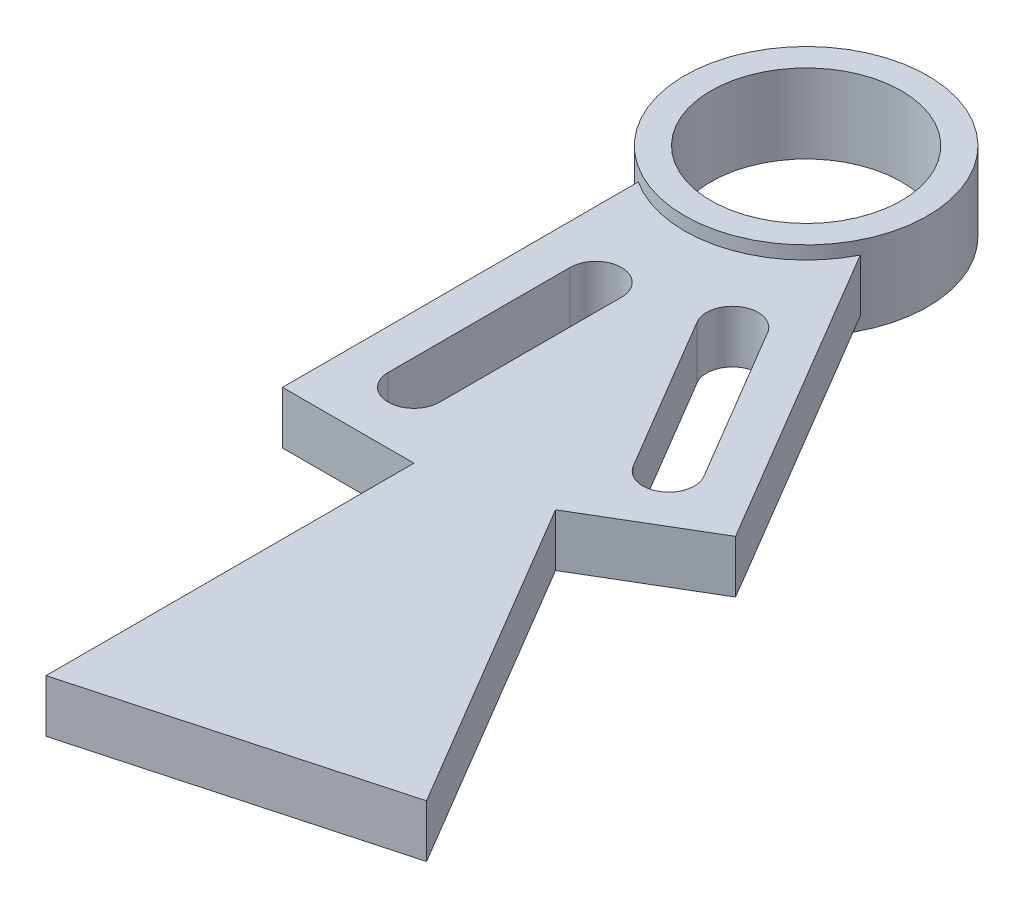
SolidWorks part; units mm, degrees
material "AISI 4130 Steel, annealed at 865C"
ref_plane "Front Plane" through (0, 0, 0) normal (0, 0, 1) x (1, 0, 0)
ref_plane "Top Plane" through (0, 0, 0) normal (0, 1, 0) x (1, 0, 0)
ref_plane "Right Plane" through (0, 0, 0) normal (1, 0, 0) x (0, 0, -1)
sketch "Sketch1" plane through (0, 0, 0) normal (0, 1, 0) x (1, 0, 0)
  line L0 (0, -50.4952) -> (0, -14.6812) construction
  line L1 (25.7368, -43.444) -> (7.4828, -12.6311) construction
  line L2 (0, -47.3837) -> (0, -25.4127) construction
  line L5 (-3.1115, -47.3837) -> (-3.1115, -25.4127)
  line L8 (-7.9375, -55.3212) -> (7.9375, -55.3212)
  line L9 (21.3674, -51.6418) -> (35.0256, -43.5505)
  line L10 (-7.9375, -55.3212) -> (-7.9375, -12.3505)
  line L11 (35.0256, -43.5505) -> (13.124, -6.5802)
  line L12 (7.9375, -55.3212) -> (7.9375, -99.7712)
  line L13 (21.3674, -51.6418) -> (44.023, -89.8848)
  line L14 (7.9375, -99.7712) -> (44.023, -89.8848)
  line L15 (0, -14.6812) -> (0, 0) construction
  line L16 (0, -55.3212) -> (0, -50.4952) construction
  line L17 (28.1965, -47.5961) -> (25.7368, -43.444)
  line L18 (3.1115, -47.3837) -> (3.1115, -25.4127)
  line L19 (12.9525, -21.8641) -> (24.1509, -40.767) construction
  line L20 (15.6295, -20.2782) -> (26.8279, -39.1811)
  line L21 (10.2755, -23.45) -> (21.4739, -42.3529)
  line L22 (7.4828, -12.6311) -> (0, 0) construction
  line L23 (0, 0) -> (20.1347, -73.4917) construction
  line L25 (181.4136, -306.2286) -> (14.7666, -24.9262) construction
  line L27 (0, 0) -> (25.9803, -94.828) construction
  circle A0 centre (0, 0) radius 11.5062
  circle A1 centre (0, 0) radius 14.6812
  arc A2 (-3.1115, -47.3837) -> (3.1115, -47.3837) centre (0, -47.3837) ccw
  arc A3 (3.1115, -25.4127) -> (-3.1115, -25.4127) centre (0, -25.4127) ccw
  arc A4 (15.6295, -20.2782) -> (10.2755, -23.45) centre (12.9525, -21.8641) ccw
  arc A5 (21.4739, -42.3529) -> (26.8279, -39.1811) centre (24.1509, -40.767) ccw
  point P9 (0, -36.3982)
  point P14 (18.5517, -31.3155)
  point P23 (0, -55.3212)
  point P26 (28.1965, -47.5961)
  point P33 (0, -50.4952)
  point P36 (25.7368, -43.444)
  point P38 (0, -22.3012)
  dimension "D2" = 29.3624
  dimension "D3" = 40.64
  dimension "D4" = 4.826
  dimension "D6" = 44.45
  dimension "D7" = 7.9375
  dimension "D5" = 4.826
  dimension "D8" = 7.62
  dimension "D9" = 76.2
extrude "Bearing extrude" add sketch "Sketch1" along normal mid plane 9.525 contours A1 A0 region at (-6.8368, 0, -12.521)
extrude "Boss-Extrude2" add sketch "Sketch1<5>" along normal mid plane 6.35 contours A1 L10 L8 L12 L14 L13 L9 L11 A4 A2 region at (15.3611, 0, 56.0678)
sketch "Sketch1<5>" plane through (0, 0, 0) normal (0, 1, 0) x (1, 0, 0) same geometry as "Sketch1"
sketch3d "Tab Point"
  line L0 (20.1347, 0, 73.4917) -> (20.1347, 23.7085, 73.4917) construction
  line L1 (0, 0, 0) -> (20.1347, 0, 73.4917) construction
  line L2 (0, 0, 0) -> (25.9803, 0, 94.828) construction
equation "\"Apex_thickness\"= .25"
equation "\"Bearing_diameter\"= .906"
equation "\"A-arm_angle\"= 32.91"
equation "\"D1@Sketch1\"=\"Bearing_diameter\""
equation "\"D1@Boss-Extrude2\"= \"Apex_thickness\""
equation "\"apex slot\"= 1.4"
equation "\"tube diameter\"= 5 / 8"
